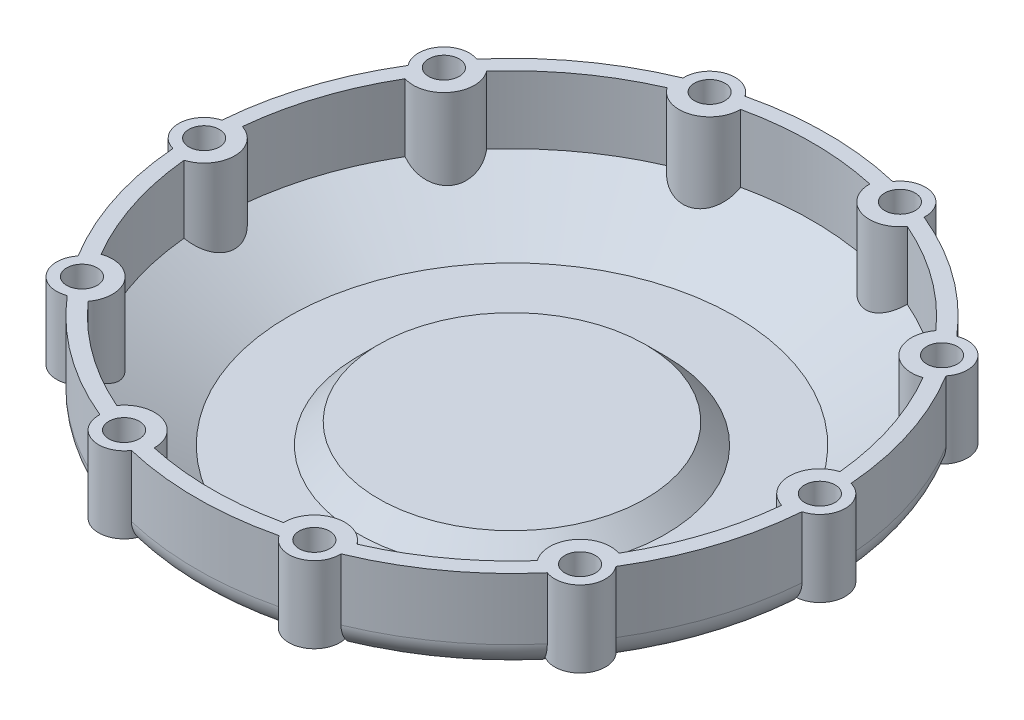
SolidWorks part; units mm, degrees
material "A356-T6 cast aluminum alloy"
ref_plane "Front Plane" through (0, 0, 0) normal (1, 0, 0) x (0, 1, 0)
ref_plane "Top Plane" through (0, 0, 0) normal (0, 0, 1) x (0, 1, 0)
ref_plane "Right Plane" through (0, 0, 0) normal (0, 1, 0) x (-1, 0, 0)
sketch "Sketch1" plane through (0, 0, 0) normal (1, 0, 0) x (0, 1, 0)
  line L0 (0, 66.9088) -> (0, -66.0551) construction
  line L1 (-99.9667, 0) -> (114.3121, 0) construction
  line L2 (0, 62) -> (15, 62)
  line L3 (0, 62) -> (-10, 44.6795)
  line L4 (-10, 44.6795) -> (-10, 29)
  line L5 (-10, 29) -> (-6, 25)
  line L6 (-6, 25) -> (-6, 0)
  line L7 (-3, 26.2426) -> (-3, 0)
  line L8 (-7, 30.2426) -> (-3, 26.2426)
  line L9 (-7, 43.8756) -> (-7, 30.2426)
  line L10 (1.7321, 59) -> (-7, 43.8756)
  line L11 (1.7321, 59) -> (15, 59)
  line L12 (-6, 0) -> (-3, 0)
  line L13 (15, 62) -> (15, 59)
  dimension "D1" = 124
  dimension "D2" = 15
  dimension "D3" = 21
  dimension "D4" = 25
  dimension "D5" = 120
  dimension "D6" = 25
  dimension "D7" = 45
  dimension "D8" = 3
revolve "Revolve1" add sketch "Sketch1" angle 360 about L1
fillet "Fillet1" radius 5 3 edges at (0, -10, -44.6795) (0, -10, -29) (0, -6, -25)
fillet "Fillet3" radius 5 1 edges at (0, 0, -62)
sketch "Sketch2" plane through (0, 15, 0) normal (0, 1, 0) x (-1, 0, 0)
  line L0 (-68.9647, 0) -> (95.2464, 0) construction
  line L1 (0, 70.6444) -> (0, -74.3989) construction
  circle A1 centre (-60.5, 0) radius 5
  circle A2 centre (0, 0) radius 60.5
  circle A3 centre (0, 0) radius 60.5
  circle A4 centre (-60.5, 0) radius 6
  circle A5 centre (-60.5, 0) radius 3
  point P5 (-60.5, 0)
  circle M4 centre (0, 0) radius 59
  dimension "D2" = 10
  dimension "D3" = 12
  dimension "D4" = 6
  dimension "D1" = 1.5
extrude "Cut-Extrude2" cut sketch "Sketch2<6>" against normal through all contours A1
sketch "Sketch2<6>" plane through (0, 15, 0) normal (0, 1, 0) x (-1, 0, 0) same geometry as "Sketch2"
extrude "Boss-Extrude1" add sketch "Sketch2" against normal blind 15 contours A1
extrude "Boss-Extrude3" add sketch "Sketch2<3>" against normal up to surface (12.4019 mm away) contours A4 A1 M4 | A3 A4 A1 M4 | A4 A3 A1 M4 region at (56.3108, 15, 2.948) region at (59.5023, 15, 5.3907) region at (59.5023, 15, -5.3907) up to face at (27.6516, 0.6981, 0.2677)
sketch "Sketch2<3>" plane through (0, 15, 0) normal (0, 1, 0) x (-1, 0, 0) same geometry as "Sketch2"
extrude "Cut-Extrude1" cut sketch "Sketch2<4>" against normal through all contours A5
sketch "Sketch2<4>" plane through (0, 15, 0) normal (0, 1, 0) x (-1, 0, 0) same geometry as "Sketch2"
pattern_circular "CirPattern1" count 10 over 360 about axis through (0, 2.8868, 0) along (0, 1, 0) of "Cut-Extrude1", "Boss-Extrude3", "Boss-Extrude1", "Cut-Extrude2"
sketch "Sketch3" plane through (0, 0, 0) normal (0, 0, 1) x (0, 1, 0)
  line L0 (-3.7528, -55.5) -> (-9.3301, -45.8397)
  line L1 (-9.3301, 45.8397) -> (-3.7528, 55.5)
  line L3 (-3.7528, -55.5) -> (-9.3301, -45.8397)
  line L4 (-10, -43.3397) -> (-10, -31.0711)
  line L5 (-10, 31.0711) -> (-10, 43.3397)
  line L7 (-10, -43.3397) -> (-10, -31.0711)
  line L8 (-7.4645, 26.4645) -> (-8.5355, 27.5355)
  line L9 (-8.5355, -27.5355) -> (-7.4645, -26.4645)
  line L10 (-8.5355, -27.5355) -> (-7.4645, -26.4645)
  line L12 (-6, -22.9289) -> (-6, 22.9289)
  line L13 (-6, -22.9289) -> (-6, 0)
  line L14 (-30.9019, 0) -> (42.8606, 0) construction
  arc A0 (-10, -43.3397) -> (-9.3301, -45.8397) centre (-5, -43.3397) ccw
  arc A1 (-9.3301, 45.8397) -> (-10, 43.3397) centre (-5, 43.3397) ccw
  arc A3 (-10, -43.3397) -> (-9.3301, -45.8397) centre (-5, -43.3397) ccw
  arc A4 (-8.5355, -27.5355) -> (-10, -31.0711) centre (-5, -31.0711) ccw
  arc A5 (-10, 31.0711) -> (-8.5355, 27.5355) centre (-5, 31.0711) ccw
  arc A7 (-8.5355, -27.5355) -> (-10, -31.0711) centre (-5, -31.0711) ccw
  arc A8 (-7.4645, -26.4645) -> (-6, -22.9289) centre (-11, -22.9289) ccw
  arc A9 (-6, 22.9289) -> (-7.4645, 26.4645) centre (-11, 22.9289) ccw
  arc A11 (-7.4645, -26.4645) -> (-6, -22.9289) centre (-11, -22.9289) ccw
ref_plane "Plane1" through (55.5, 0, 0) normal (1, 0, 0) x (0, 1, 0)
sketch "Sketch4" plane through (55.5, 0, 0) normal (1, 0, 0) x (0, 1, 0)
  circle A0 centre (-3.7599, 0) radius 1
  point P0 (-3.7599, 0)
  dimension "D1" = 2
sweep "Sweep1" add profiles "Sketch4" path "Sketch3"
pattern_circular "CirPattern2" count 10 over 360 about axis through (0, -1.4434, 0) along (0, -1, 0) of "Sweep1"
ref_axis "Axis1" through (0, 0, 68.7928) along (0, 0, -1)
